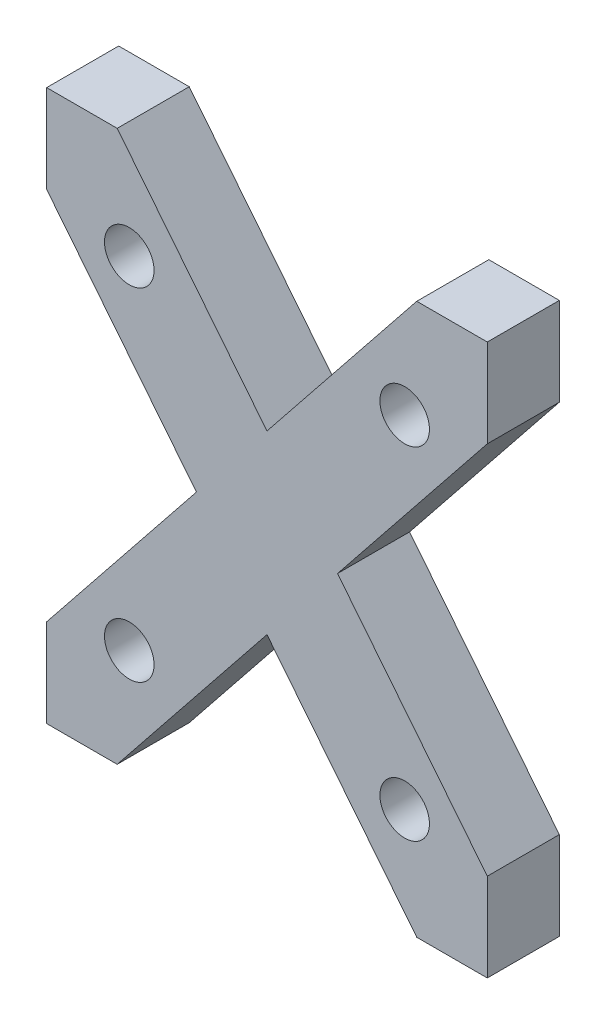
SolidWorks part; units mm, degrees
ref_plane "Front Plane" through (0, 0, 0) normal (0, 0, 1) x (1, 0, 0)
ref_plane "Top Plane" through (0, 0, 0) normal (0, 1, 0) x (1, 0, 0)
ref_plane "Right Plane" through (0, 0, 0) normal (1, 0, 0) x (0, 0, -1)
sketch "Sketch1" plane through (0, 0, 0) normal (0, 0, 1) x (1, 0, 0)
  line L0 (0, 0) -> (0, 25) construction
  line L1 (-20, -25) -> (20, -25)
  line L2 (-20, -25) -> (-20, 25)
  line L3 (-20, 25) -> (20, 25)
  line L4 (20, -25) -> (20, 25)
  line L5 (-20, -25) -> (20, 25) construction
  line L6 (-20, 25) -> (20, -25) construction
  point P0 (0, 0)
  point P6 (12.5, 15.5)
  point P9 (12.5, -15.5)
  point P10 (-12.5, -15.5)
  point P11 (-12.5, 15.5)
  dimension "D1" = 7.5
  dimension "D2" = 7.5
  dimension "D3" = 31
  dimension "D5" = 9.5
  dimension "D6" = 50
  dimension "D7" = 40
  dimension "D8" = 9.5
extrude "Boss-Extrude1" add sketch "Sketch1" along normal blind 6.54
hole_wizard "M4 Clearance Hole1" positions "Sketch4" profile "Sketch5" hole size "M4" standard "ISO" end condition through all
sketch "Sketch4" plane through (0, 0, 0) normal (0, 0, -1) x (-1, 0, 0)
  point P0 (-12.5, 15.5)
  point P3 (12.5, 15.5)
  point P6 (12.5, -15.5)
  point P9 (-12.5, -15.5)
sketch "Sketch5" plane through (12.5, 15.5, 0) normal (1, 0, 0) x (0, 1, 0)
  line L0 (0, 0) -> (0, 6.54)
  line L1 (0, 6.54) -> (2.25, 6.54)
  line L2 (2.25, 6.54) -> (2.25, 0)
  line L5 (2.25, 0) -> (0, 0)
  line L11 (0, -6.35) -> (0, 107.95) construction
  dimension "Thru Hole Dia." = 4.5
  dimension "Thru Hole Depth" = 6.54
sketch "Sketch6" plane through (0, 0, 0) normal (0, 0, -1) x (-1, 0, 0)
  line L0 (20, 16.9961) -> (20, -16.9961)
  line L2 (20, 25) -> (20, -25) construction
  line L6 (20, -16.9961) -> (6.4031, 0)
  line L7 (6.4031, 0) -> (20, 16.9961)
  line L8 (13.5969, -25) -> (-13.5969, -25)
  line L9 (20, -25) -> (-20, -25) construction
  line L10 (-13.5969, -25) -> (0, -8.0039)
  line L11 (0, -8.0039) -> (13.5969, -25)
  line L12 (-20, 16.9961) -> (-20, -16.9961)
  line L13 (-20, -25) -> (-20, 25) construction
  line L14 (-20, -16.9961) -> (-6.4031, 0)
  line L15 (-6.4031, 0) -> (-20, 16.9961)
  line L16 (-13.5969, 25) -> (13.5969, 25)
  line L17 (-20, 25) -> (20, 25) construction
  line L18 (13.5969, 25) -> (0, 8.0039)
  line L19 (0, 8.0039) -> (-13.5969, 25)
extrude "Cut-Extrude1" cut sketch "Sketch6" against normal through all
